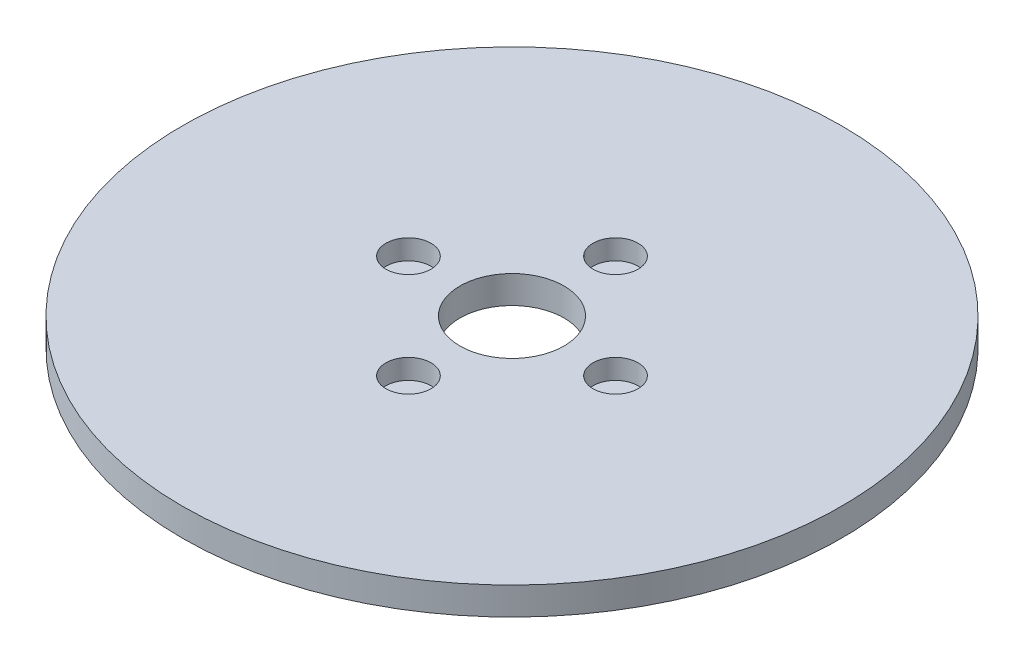
SolidWorks part; units mm, degrees
ref_plane "Front Plane" through (0, 0, 0) normal (0, 0, 1) x (1, 0, 0)
ref_plane "Top Plane" through (0, 0, 0) normal (0, 1, 0) x (1, 0, 0)
ref_plane "Right Plane" through (0, 0, 0) normal (1, 0, 0) x (0, 0, -1)
sketch "Sketch1" plane through (0, 0, 0) normal (0, 1, 0) x (1, 0, 0)
  circle A0 centre (0, 0) radius 95
  dimension "FLANGE_OD" = 190
extrude "Boss-Extrude1" add sketch "Sketch1" along normal blind 8
sketch "Sketch2" plane through (0, 0, 0) normal (0, 1, 0) x (1, 0, 0)
  circle A0 centre (0, 0) radius 15
  dimension "BORE_D" = 30
extrude "Cut-Extrude1" cut sketch "Sketch2" along normal through all
sketch "Sketch3" plane through (0, 8, 0) normal (0, 1, 0) x (1, 0, 0)
  circle A0 centre (0, 0) radius 29.846 construction
  circle A1 centre (-29.846, 0) radius 6.4975
  dimension "BOLT_D" = 12.9949
  dimension "BOLT_PCD" = 59.6921
extrude "Cut-Extrude2" cut sketch "Sketch3" against normal blind 5.7473
pattern_circular "CirPattern1" count 4 over 360 about axis through (0, 0, 0) along (0, 1, 0) of "Cut-Extrude2"
